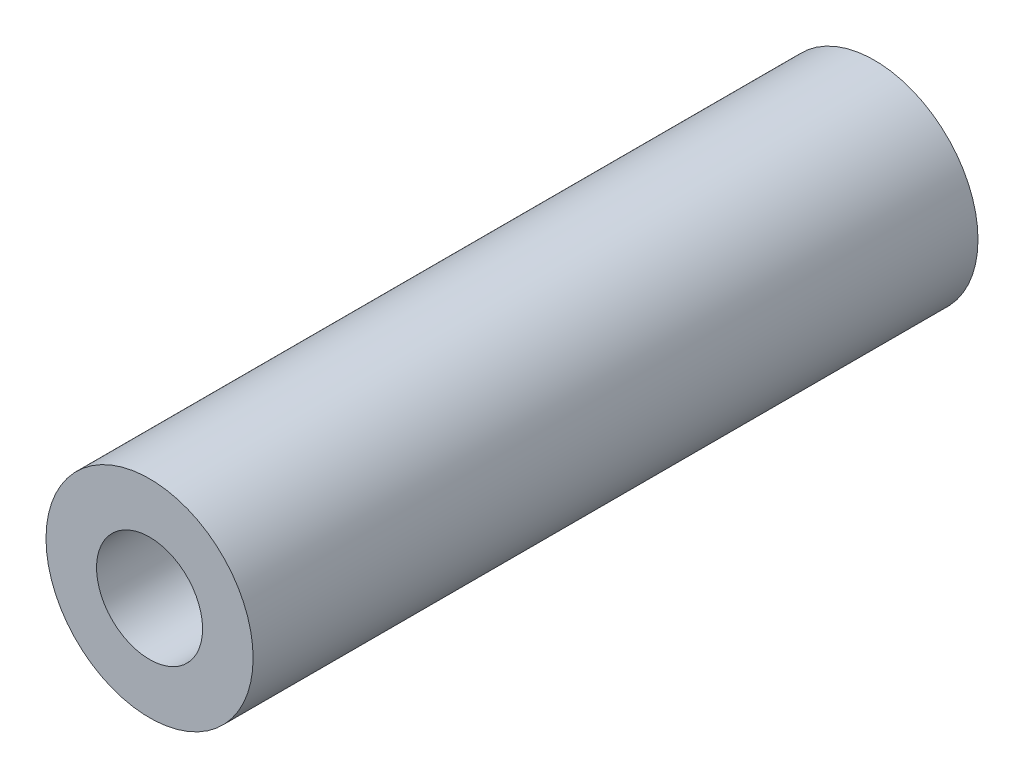
SolidWorks part; units mm, degrees
ref_plane "Front Plane" through (0, 0, 0) normal (0, 0, 1) x (1, 0, 0)
ref_plane "Top Plane" through (0, 0, 0) normal (0, 1, 0) x (1, 0, 0)
ref_plane "Right Plane" through (0, 0, 0) normal (1, 0, 0) x (0, 0, -1)
sketch "Sketch1" plane through (0, 0, 0) normal (0, 0, 1) x (1, 0, 0)
  circle A0 centre (0, 0) radius 4.7625
  circle A1 centre (0, 0) radius 2.4384
  dimension "OD" = 9.525
  dimension "ID" = 4.8768
extrude "Extrude1" add sketch "Sketch1" along normal mid plane 33.3375
sketch "Sketch2" plane through (0, 0, 0) normal (1, 0, 0) x (0, 0, -1)
  line L0 (-16.6687, -2.4384) -> (16.6687, -2.4384) construction
  line L3 (16.6687, 2.4384) -> (-16.6687, 2.4384) construction
  line L5 (-16.6687, -2.4384) -> (16.6687, -2.4384)
  line L6 (16.6687, 2.4384) -> (-16.6687, 2.4384)
sketch "Sketch4" plane through (0, 0, 16.6687) normal (0, 0, 1) x (1, 0, 0)
  line L0 (0, 0) -> (-1.7242, 1.7242)
  line L1 (0, -5.2388) -> (0, 5.2388) construction
  circle A0 centre (0, 0) radius 2.4384 construction
  dimension "D1" = 45
